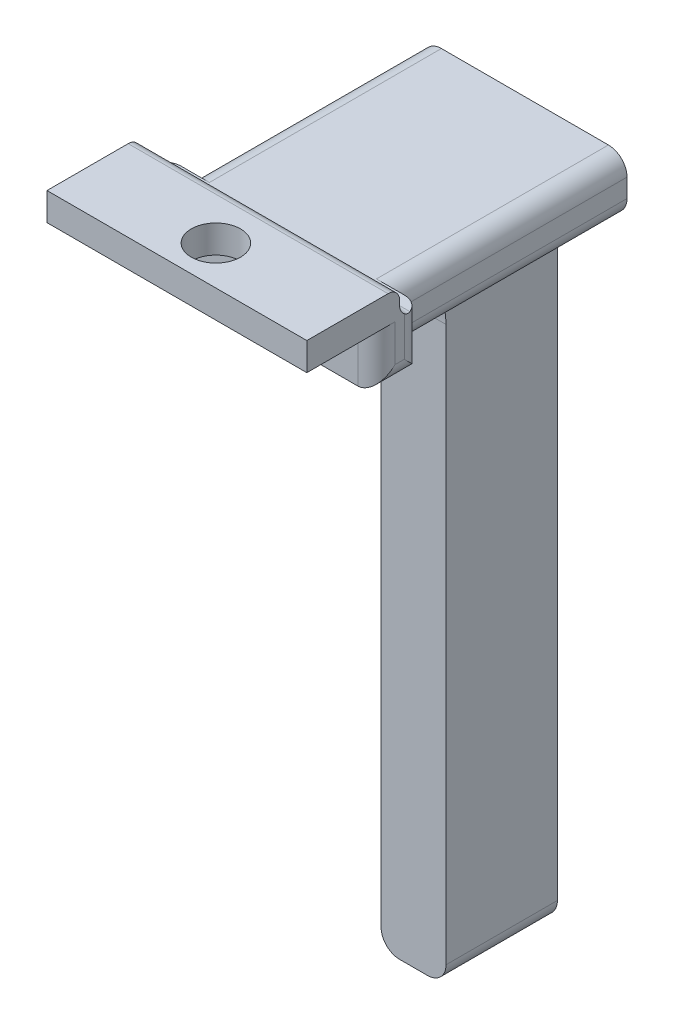
SolidWorks part; units mm, degrees
ref_plane "Alzado" through (0, 0, 0) normal (0, 0, 1) x (1, 0, 0)
ref_plane "Planta" through (0, 0, 0) normal (0, 1, 0) x (1, 0, 0)
ref_plane "Vista lateral" through (0, 0, 0) normal (1, 0, 0) x (0, 0, -1)
sketch "Croquis1" plane through (0, 0, 0) normal (0, 1, 0) x (1, 0, 0)
  line L0 (-14, 0) -> (14, 0)
  line L1 (14, 0) -> (14, 5)
  line L2 (14, 5) -> (11, 5)
  line L3 (11, 5) -> (11, 30)
  line L4 (-14, 0) -> (-14, 5)
  line L5 (-14, 5) -> (-11, 5)
  line L6 (-11, 5) -> (-11, 30)
  line L7 (-11, 30) -> (11, 30)
  point P10 (0, 0)
  dimension "D1" = 3
  dimension "D2" = 5
  dimension "D3" = 28
  dimension "D4" = 25
extrude "Saliente-Extruir1" add sketch "Croquis1" along normal blind 6
sketch "Croquis2" plane through (0, 0, 0) normal (0, 0, 1) x (1, 0, 0)
  line L0 (-14, 6) -> (14, 6) construction
  line L1 (3.5, 6) -> (-3.5, 6)
  line L2 (3.5, 6) -> (3.5, -69.25)
  line L3 (3.5, -69.25) -> (-3.5, -69.25)
  line L4 (-3.5, 6) -> (-3.5, -69.25)
  line L6 (-1.725, 4) -> (1.725, 4)
  line L7 (-1.725, 4) -> (-1.725, -67.75)
  line L8 (-1.725, -67.75) -> (1.725, -67.75)
  line L9 (1.725, 4) -> (1.725, -67.75)
  point P6 (0, 6)
  point P12 (0, 4)
  dimension "D1" = 7
  dimension "D2" = 3.45
  dimension "D3" = 2
  dimension "D4" = 71.75
  dimension "D5" = 1.5
extrude "Saliente-Extruir2" add sketch "Croquis2" against normal up to surface (30 mm away) from offset 23 up to face at (0, 3, -30) offset against normal yes
extrude "Cortar-Extruir1" cut sketch "Croquis2<2>" along normal up to surface (-23 mm away) from surface contours L9 L6 L7 L8 region at (0, -31.875, 0) up to face at (0, -34.25, -23) starting at face at (0, -15.8125, -30)
sketch "Croquis2<2>" plane through (0, 0, 0) normal (0, 0, 1) x (1, 0, 0) same geometry as "Croquis2"
sketch "Croquis3" plane through (0, 0, -23) normal (0, 0, -1) x (-1, 0, 0)
  line L0 (-11, 6) -> (11, 6) construction
  line L1 (3.5, -69.25) -> (-3.5, -69.25)
  line L2 (3.5, -69.25) -> (3.5, 6)
  line L3 (3.5, 6) -> (-3.5, 6)
  line L4 (-3.5, -69.25) -> (-3.5, 6)
  line L5 (-3.5, 0) -> (-3.5, -69.25) construction
extrude "Saliente-Extruir3" add sketch "Croquis3" along normal blind 2 and the other way blind 5
fillet "Redondeo1" radius 2 8 edges at (-11, 6, -17.5) (11, 6, -17.5) (3.5, 0, -24) (11, 0, -17.5) (-11, 0, -17.5) (-3.5, 0, -24) (3.5, -69.25, -24) (-3.5, -69.25, -24)
fillet "Redondeo2" radius 7.5 1 edges at (0, 0, -18)
sketch "Croquis4" plane through (0, 6, 0) normal (0, 1, 0) x (1, 0, 0)
  line L0 (-14, 2.5) -> (-14, -7.5)
  line L1 (-14, -7.5) -> (14, -7.5)
  line L2 (14, -7.5) -> (14, 2.5)
  line L4 (-14, 0) -> (14, 0) construction
  line L5 (-14, 0) -> (14, 0)
  line L6 (-14, 5) -> (-14, 0) construction
  line L7 (14, 0) -> (14, 5) construction
  line L8 (-14, 2.5) -> (14, 2.5)
  circle A0 centre (0, -3.3) radius 2.65
  line M7 (-9, 5) -> (-14, 5)
  line M8 (-14, 5) -> (-14, 0)
  line M9 (-14, 0) -> (14, 0)
  line M10 (14, 0) -> (14, 5)
  line M11 (14, 5) -> (9, 5)
  dimension "D2" = 5.3
  dimension "D1" = 7.5
  dimension "D3" = 3.3
extrude "Saliente-Extruir4" add sketch "Croquis4" along normal blind 3 contours L1 L2 L0 M9 | L8 M7 M8 M9 M10 M11 region at (0, 6, -1.25) region at (0, 6, 0.2899)
fillet "Redondeo3" radius 1.25 2 edges at (0, 9, -2.5) (0, 6, -2.5)
fillet "Redondeo4" radius 2 6 edges at (-14, 3, -5) (-14, 0, -2.5) (-14, 3, 0) (14, 3, -5) (14, 0, -2.5) (14, 3, 0)
